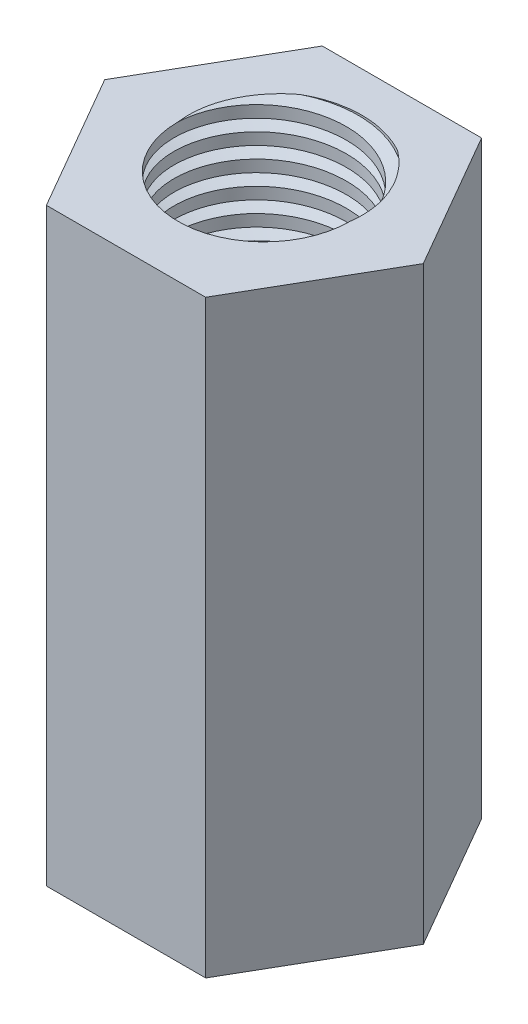
SolidWorks part; units mm, degrees
note: The reader was unsure of these and kept them because the rebuilt part matched: shared geometry of "草图1<3>".
ref_plane "前视基准面" through (0, 0, 0) normal (0, 0, 1) x (1, 0, 0)
ref_plane "上视基准面" through (0, 0, 0) normal (0, 1, 0) x (1, 0, 0)
ref_plane "右视基准面" through (0, 0, 0) normal (1, 0, 0) x (0, 0, -1)
sketch "草图1" plane through (0, 0, 0) normal (0, 1, 0) x (1, 0, 0)
  line L0 (0, 0) -> (0, 4.5761) construction
  line L1 (1.351, -2.34) -> (2.702, 0)
  line L2 (2.702, 0) -> (1.351, 2.34)
  line L3 (1.351, 2.34) -> (-1.351, 2.34)
  line L4 (-1.351, 2.34) -> (-2.702, 0)
  line L5 (-2.702, 0) -> (-1.351, -2.34)
  line L6 (-1.351, -2.34) -> (1.351, -2.34)
  line L7 (0, 4.5761) -> (0, -3.6794) construction
  circle A0 centre (0, 0) radius 2.34 construction
  circle A1 centre (0, 0) radius 1.46
  dimension "D1" = 4.68
  dimension "D2" = 2.92
extrude "凸台-拉伸1" add sketch "草图1" along normal blind 10 contours A1 | L5 L6 L1 L2 L3 L4 A1
extrude "切除-拉伸1" cut sketch "草图1<3>" along normal blind 5 contours A1
sketch "草图1<3>" plane through (0, 0, 0) normal (0, 1, 0) x (1, 0, 0) same geometry as "草图1"
ref_plane "基准面1" through (0, 0, 0) normal (0, 0, -1) x (-1, 0, 0)
ref_plane "基准面2" through (0, 10.1, 0) normal (0, 1, 0) x (1, 0, 0)
sketch "草图6" plane through (0, 0, 0) normal (0, -1, 0) x (1, 0, 0)
  circle A0 centre (0, 0) radius 1.46
curve "螺旋线/涡状线2" pitch 0.4 height 30 turns 75
sketch "草图7" plane through (0, 0, 0) normal (0, 0, -1) x (-1, 0, 0)
  line L0 (1.46, 0.2) -> (1.66, 0.1333)
  line L1 (1.66, 0.0667) -> (1.46, 0)
  line L2 (1.46, 0.2) -> (1.46, 0)
  line L3 (1.66, 0.1333) -> (1.66, 0.0667)
  line L8 (1.351, 0) -> (-1.351, 0) construction
  dimension "D1" = 0.2
  dimension "D3" = 1.46
  dimension "D4" = 0.2
sweep "切除-扫描2" cut profiles "草图7" path "螺旋线/涡状线2"
sketch "Sketch1" plane through (0, 10, 0) normal (0, 1, 0) x (1, 0, 0)
  circle A0 centre (0, 0) radius 1.46
  dimension "D1" = 2.92
extrude "Cut-Extrude1" cut sketch "Sketch1" against normal blind 5
equation "\"chang\"= 20mm"
equation "\"r\"= 2.92mm"
equation "\"luowengao\"= 6.5mm"
equation "\"rr\"= 4.68mm"
equation "\"D1@草图1\"=\"rr\""
equation "\"D2@草图1\"=\"r\""
equation "\"D1@凸台-拉伸1\"=\"chang\""
equation "\"D1@切除-拉伸1\"=\"luowengao\"+5mm"
equation "\"D1@草图2\"=\"r\""
equation "\"D1@凸台-拉伸2\"=\"luowengao\""
